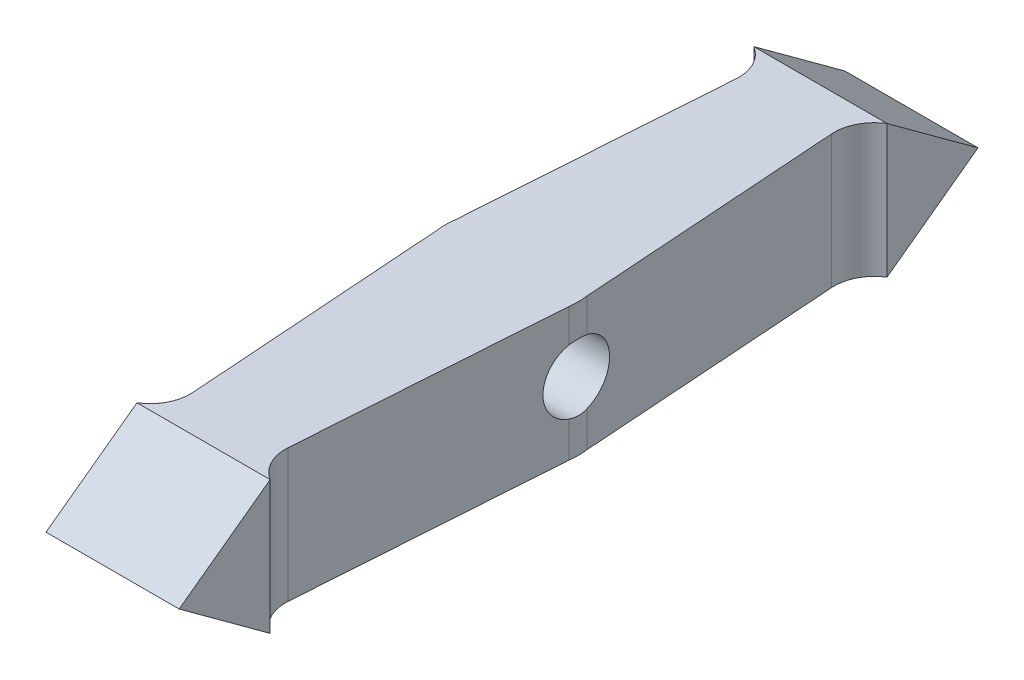
SolidWorks part; units mm, degrees
ref_plane "Front Plane" through (0, 0, 0) normal (0, 0, 1) x (1, 0, 0)
ref_plane "Top Plane" through (0, 0, 0) normal (0, 1, 0) x (1, 0, 0)
ref_plane "Right Plane" through (0, 0, 0) normal (1, 0, 0) x (0, 0, -1)
sketch "Sketch1" plane through (0, 0, 0) normal (1, 0, 0) x (0, 0, -1)
  line L0 (-76.6337, 0.4666) -> (-59.2717, 13.1666)
  line L1 (-59.2717, 13.1666) -> (58.4043, 13.1666)
  line L3 (-59.2717, -12.2334) -> (58.4043, -12.2334)
  line L8 (-59.2717, -12.2334) -> (-76.6337, 0.4666)
  line L11 (75.7663, 0.4666) -> (58.4043, 13.1666)
  line L12 (58.4043, -12.2334) -> (75.7663, 0.4666)
  point P0 (0, 0)
extrude "Boss-Extrude1" add sketch "Sketch1" along normal blind 25.4 contours L1 L11 L12 L3 L8 L0
sketch "Sketch4" plane through (0, 13.1666, 0) normal (0, 1, 0) x (1, 0, 0)
  line L0 (25.4, -0.4337) -> (0, -0.4337)
  line L1 (25.4, -59.2717) -> (25.4, 58.4043) construction
  line L2 (0, -59.2717) -> (0, 58.4043) construction
  line L3 (25.4, -0.4337) -> (21.3501, 58.4043)
  line L5 (25.4, 58.4043) -> (0, 58.4043) construction
  line L6 (0, 58.4043) -> (4.1129, 58.4043)
  line L7 (4.1129, 58.4043) -> (0, -0.4337)
  line L8 (21.3501, -59.2717) -> (25.4, -0.4337)
  line L9 (25.4, -59.2717) -> (0, -59.2717) construction
  line L10 (21.3501, -59.2717) -> (4.1129, -59.2717)
  line L11 (4.1129, -59.2717) -> (0, -0.4337)
  line L12 (25.4, -0.4337) -> (25.4, -59.2717)
  line L13 (25.4, -59.2717) -> (0, -59.2717)
  line L14 (0, -59.2717) -> (0, 58.4043)
  line L15 (25.4, 58.4043) -> (25.4, -59.2717)
  circle A0 centre (12.7, -0.4337) radius 6.35
  circle A1 centre (12.7, -0.4337) radius 12.7
  line M2 (0, 58.4043) -> (0, -59.2717)
  line M3 (0, -59.2717) -> (25.4, -59.2717)
  line M4 (25.4, -59.2717) -> (25.4, 58.4043)
  line M5 (25.4, 58.4043) -> (0, 58.4043)
extrude "Cut-Extrude2" cut sketch "Sketch4" against normal through all both contours A1 L8 M3 M4 | A1 L11 M2 M3 | A1 L7 M5 M2 | A1 L3 M4 M5 region at (24.0496, 13.1666, -38.8029) region at (24.0496, 13.1666, 39.6702) region at (1.3714, 13.1666, -38.8032) region at (1.3714, 13.1666, 39.6706)
fillet "Fillet1" radius 7.62 4 edges at (21.3501, 0.4666, 59.2717) (4.1129, 0.4666, 59.2717) (4.1129, 0.4666, -58.4043) (21.3501, 0.4666, -58.4043)
ref_plane "Plane1" through (25.4, 0, 0) normal (1, 0, 0) x (0, 0, -1)
sketch "Sketch5" plane through (25.4, 0, 0) normal (1, 0, 0) x (0, 0, -1)
  circle A1 centre (-0.4337, 0.6802) radius 6.35
extrude "Cut-Extrude3" cut sketch "Sketch5" against normal through all both and the other way through all contours A1
